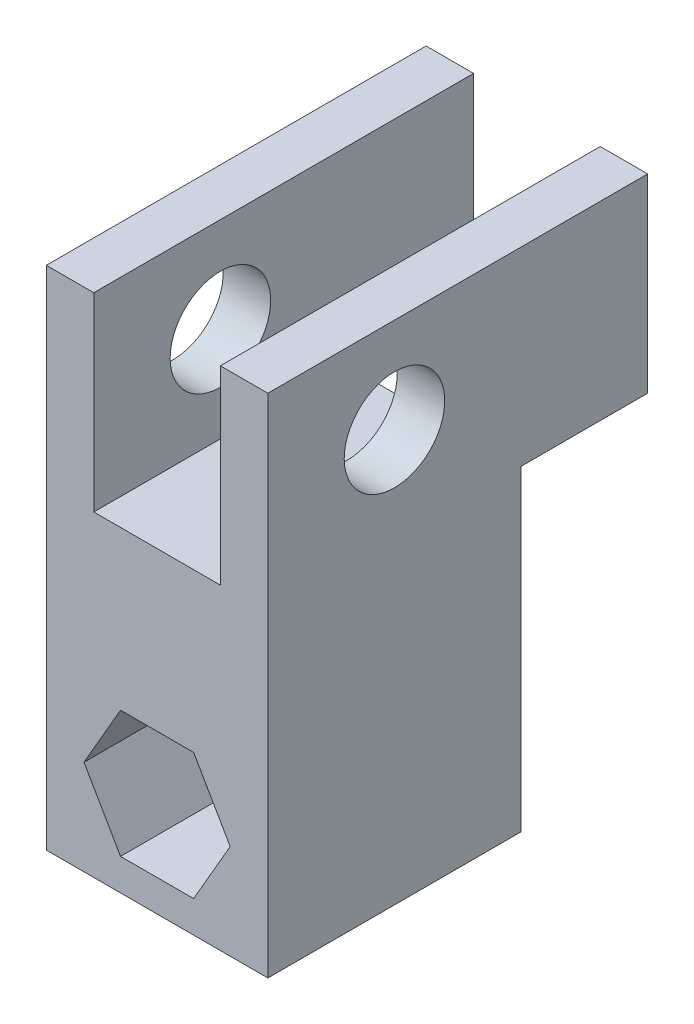
SolidWorks part; units mm, degrees
material "6061-T6 (SS)"
ref_plane "Front" through (0, 0, 0) normal (0, 0, 1) x (1, 0, 0)
ref_plane "Top" through (0, 0, 0) normal (0, 1, 0) x (1, 0, 0)
ref_plane "Right" through (0, 0, 0) normal (1, 0, 0) x (0, 0, -1)
sketch "Sketch1" plane through (0, 0, 0) normal (0, 0, 1) x (1, 0, 0)
  line L0 (-11.1125, 0) -> (11.1125, 0)
  line L1 (-11.1125, 0) -> (-11.1125, 50.8)
  line L2 (-11.1125, 50.8) -> (-6.35, 50.8)
  line L3 (-6.35, 50.8) -> (-6.35, 31.75)
  line L4 (-6.35, 31.75) -> (6.35, 31.75)
  line L5 (6.35, 31.75) -> (6.35, 50.8)
  line L6 (6.35, 50.8) -> (11.1125, 50.8)
  line L7 (11.1125, 50.8) -> (11.1125, 0)
  point P4 (0, 0)
  dimension "D1" = 22.225
  dimension "D2" = 50.8
  dimension "D3" = 12.7
  dimension "D4" = 19.05
extrude "Boss-Extrude1" add sketch "Sketch1" along normal blind 25.4
sketch "Sketch2" plane through (0, 0, 25.4) normal (0, 0, 1) x (1, 0, 0)
  line L0 (0, 0) -> (0, 3.175) construction
  line L1 (3.6662, 15.875) -> (-3.6662, 15.875)
  line L2 (-3.6662, 15.875) -> (-7.3323, 9.525)
  line L3 (-7.3323, 9.525) -> (-3.6662, 3.175)
  line L4 (-3.6662, 3.175) -> (3.6662, 3.175)
  line L5 (3.6662, 3.175) -> (7.3323, 9.525)
  line L6 (7.3323, 9.525) -> (3.6662, 15.875)
  line L7 (-11.1125, 0) -> (11.1125, 0) construction
  circle A0 centre (0, 9.525) radius 6.35 construction
  dimension "D1" = 12.7
  dimension "D2" = 9.525
extrude "Cut-Extrude1" cut sketch "Sketch2" against normal through all
sketch "Sketch6" plane through (-11.1125, 0, 0) normal (-1, 0, 0) x (0, 0, 1)
  line L0 (25.4, 50.8) -> (0, 50.8) construction
  line L2 (12.7, 41.275) -> (25.4, 41.275) construction
  line L3 (25.4, 50.8) -> (25.4, 0) construction
  line L5 (12.7, 41.275) -> (0, 41.275) construction
  line L6 (0, 50.8) -> (0, 0) construction
  point P0 (12.7, 41.275)
  dimension "D1" = 9.525
hole_wizard "3/8 Clearance Hole1" positions "Sketch6" profile "Sketch4" hole size "3/8" standard "ANSI Inch" end condition through all
sketch "Sketch4" plane through (-11.1125, 41.275, 12.7) normal (0, 1, 0) x (0, 0, 1)
  line L0 (0, 0) -> (0, 22.225)
  line L1 (0, 22.225) -> (5.0419, 22.225)
  line L2 (5.0419, 22.225) -> (5.0419, 0)
  line L5 (5.0419, 0) -> (0, 0)
  line L11 (0, -6.35) -> (0, 107.95) construction
  dimension "Thru Hole Dia." = 10.0838
  dimension "Thru Hole Depth" = 22.225
sketch "Sketch7" plane through (0, 0, 0) normal (0, 0, -1) x (-1, 0, 0)
  line L1 (-11.1125, 50.8) -> (-6.35, 50.8)
  line L2 (-11.1125, 50.8) -> (-11.1125, 31.75)
  line L3 (-11.1125, 31.75) -> (-6.35, 31.75)
  line L4 (-6.35, 50.8) -> (-6.35, 31.75)
  line L5 (11.1125, 50.8) -> (6.35, 50.8)
  line L6 (11.1125, 50.8) -> (11.1125, 31.75)
  line L7 (11.1125, 31.75) -> (6.35, 31.75)
  line L8 (6.35, 50.8) -> (6.35, 31.75)
extrude "Boss-Extrude2" add sketch "Sketch7" along normal blind 12.7
